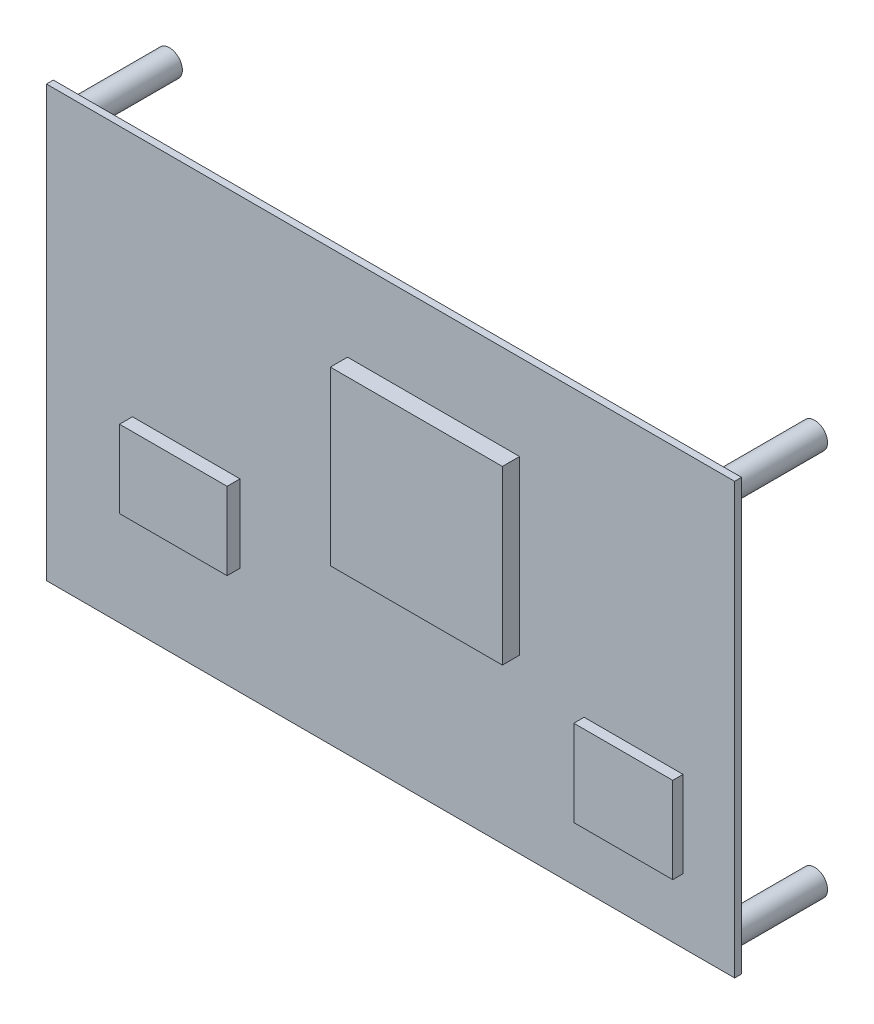
SolidWorks part; units mm, degrees
material "E-Glass Fiber"
ref_plane "Front Plane" through (0, 0, 0) normal (0, 0, 1) x (1, 0, 0)
ref_plane "Top Plane" through (0, 0, 0) normal (0, 1, 0) x (1, 0, 0)
ref_plane "Right Plane" through (0, 0, 0) normal (1, 0, 0) x (0, 0, -1)
sketch "Extrude sketch 1" plane through (0, 0, 0) normal (0, 0, 1) x (1, 0, 0)
  line L0 (477, 5) -> (637, 5)
  line L1 (637, 5) -> (637, 105)
  line L2 (637, 105) -> (477, 105)
  line L3 (477, 105) -> (477, 5)
  dimension "D1" = 160
  dimension "D2" = 100
extrude "Extrude 1" add sketch "Extrude sketch 1" along normal blind 1.6 from offset 345 separate body
sketch "Extrude sketch 2" plane through (0, 0, 0) normal (0, 0, 1) x (1, 0, 0)
  line L0 (497, 30) -> (522, 30)
  line L1 (522, 30) -> (522, 48)
  line L2 (522, 48) -> (497, 48)
  line L3 (497, 48) -> (497, 30)
  dimension "D1" = 25
  dimension "D2" = 18
extrude "Extrude 2" add sketch "Extrude sketch 2" along normal blind 3 from offset 346.6 separate body
sketch "Extrude sketch 3" plane through (0, 0, 0) normal (0, 0, 1) x (1, 0, 0)
  line L0 (547, 45) -> (587, 45)
  line L1 (587, 45) -> (587, 85)
  line L2 (587, 85) -> (547, 85)
  line L3 (547, 85) -> (547, 45)
  dimension "D1" = 40
extrude "Extrude 3" add sketch "Extrude sketch 3" along normal blind 4 from offset 346.6 separate body
sketch "Extrude sketch 4" plane through (0, 0, 0) normal (0, 0, 1) x (1, 0, 0)
  line L0 (602, 20) -> (625, 20)
  line L1 (625, 20) -> (625, 40)
  line L2 (625, 40) -> (602, 40)
  line L3 (602, 40) -> (602, 20)
  dimension "D1" = 23
  dimension "D2" = 20
extrude "Extrude 4" add sketch "Extrude sketch 4" along normal blind 2.4 from offset 346.6 separate body
sketch "Extrude sketch 5" plane through (0, 0, 0) normal (0, 0, 1) x (1, 0, 0)
  circle A0 centre (482, 10) radius 3
  dimension "D1" = 6
extrude "Extrude 5" add sketch "Extrude sketch 5" along normal blind 22 from offset 323 separate body
sketch "Extrude sketch 6" plane through (0, 0, 0) normal (0, 0, 1) x (1, 0, 0)
  circle A0 centre (482, 100) radius 3
  dimension "D1" = 6
extrude "Extrude 6" add sketch "Extrude sketch 6" along normal blind 22 from offset 323 separate body
sketch "Extrude sketch 7" plane through (0, 0, 0) normal (0, 0, 1) x (1, 0, 0)
  circle A0 centre (632, 10) radius 3
  dimension "D1" = 6
extrude "Extrude 7" add sketch "Extrude sketch 7" along normal blind 22 from offset 323 separate body
sketch "Extrude sketch 8" plane through (0, 0, 0) normal (0, 0, 1) x (1, 0, 0)
  circle A0 centre (632, 100) radius 3
  dimension "D1" = 6
extrude "Extrude 8" add sketch "Extrude sketch 8" along normal blind 22 from offset 323 separate body
combine bodies "Combine (weld / assembly of features)" operation type add bodies to combine 105 103 106 101 107 102 108 104
